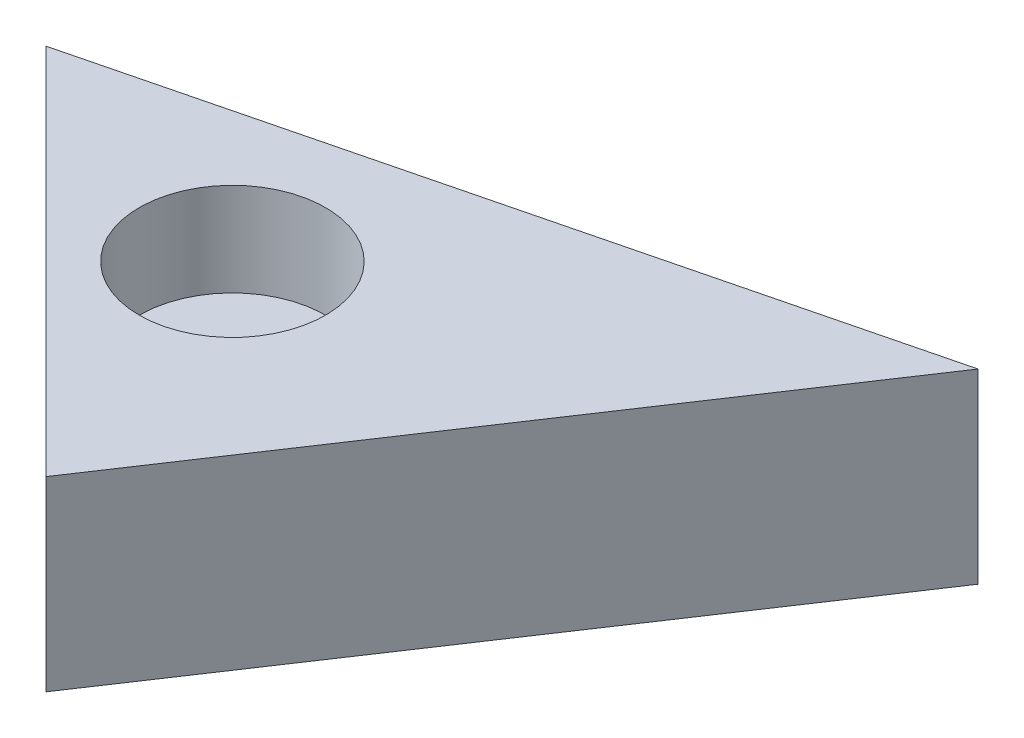
SolidWorks part; units mm, degrees
ref_plane "Front Plane" through (0, 0, 0) normal (0, 0, 1) x (1, 0, 0)
ref_plane "Top Plane" through (0, 0, 0) normal (0, 1, 0) x (1, 0, 0)
ref_plane "Right Plane" through (0, 0, 0) normal (1, 0, 0) x (0, 0, -1)
sketch "Sketch1" plane through (0, 0, 0) normal (0, 1, 0) x (1, 0, 0)
  line L0 (0, 0) -> (50.8, -50.8)
  line L1 (50.8, -50.8) -> (101.6, 25.4)
  line L2 (101.6, 25.4) -> (0, 0)
  point P4 (0, 0)
  point P5 (0, 0)
  point P6 (4.6446, -22.9326)
  dimension "D1" = 50.8
  dimension "D2" = 50.8
  dimension "D3" = 101.6
  dimension "D4" = 25.4
extrude "Boss-Extrude1" add sketch "Sketch1" along normal blind 25.4
sketch "Sketch2" plane through (0, 25.4, 0) normal (0, 1, 0) x (1, 0, 0)
  circle A0 centre (38.1, -12.7) radius 12.7
  dimension "D1" = 25.4
  dimension "D2" = 38.1
  dimension "D3" = 12.7
extrude "Cut-Extrude1" cut sketch "Sketch2" against normal blind 12.7
